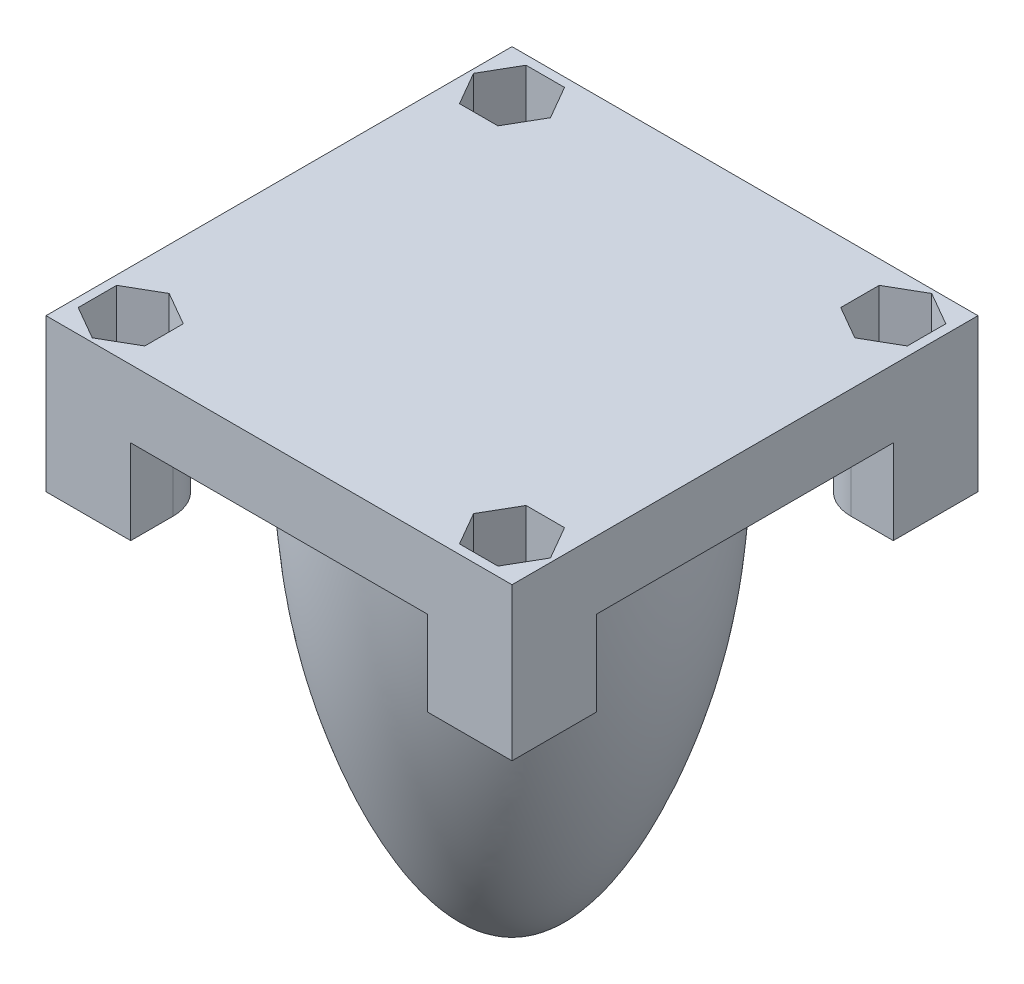
SolidWorks part; units mm, degrees
ref_plane "Front Plane" through (0, 0, 0) normal (0, 0, 1) x (1, 0, 0)
ref_plane "Top Plane" through (0, 0, 0) normal (0, 1, 0) x (1, 0, 0)
ref_plane "Right Plane" through (0, 0, 0) normal (1, 0, 0) x (0, 0, -1)
sketch "Sketch5" plane through (0, 0, 0) normal (0, 0, 1) x (1, 0, 0)
  line L0 (0, -5) -> (0, 0) construction
  line L2 (27.5, -5) -> (-27.5, -5)
  line L3 (27.5, -5) -> (27.5, 65)
  line L4 (27.5, 65) -> (-27.5, 65)
  line L5 (-27.5, -5) -> (-27.5, 65)
  line L6 (27.5, -5) -> (-27.5, 65) construction
  line L7 (27.5, 65) -> (-27.5, -5) construction
  dimension "D1" = 55
  dimension "D2" = 70
  dimension "D3" = 5
extrude "Boss-Extrude8" add sketch "Sketch5" along normal mid plane 55
sketch "Sketch1" plane through (0, 0, 0) normal (1, 0, 0) x (0, 0, -1)
  line L0 (2.2, 0) -> (4.9945, 0) construction
  line L1 (23, 55) -> (20, 55) construction
  line L2 (0, -7) -> (0, 3)
  line L3 (0, 0) -> (0, 78.0585) construction
  line L4 (23.4, 55) -> (23, 55) construction
  line L5 (0, 3) -> (-8.2525, 3) construction
  line L6 (25.4, 57) -> (304.8069, 57)
  line L7 (304.8069, 57) -> (304.8069, -311.2674)
  line L8 (304.8069, -311.2674) -> (0, -311.2674)
  line L9 (0, -311.2674) -> (0, -7)
  line L10 (2.2, 0) -> (2.2, -7) construction
  line L14 (20, 55) -> (20, 57)
  line L17 (22, 59) -> (23.4, 59)
  line L19 (2.2, -7) -> (0, -7) construction
  arc A0 (20, 57) -> (22, 59) centre (22, 57) cw
  arc A1 (25.4, 57) -> (23.4, 55) centre (23.4, 57) cw construction
  arc A2 (25.4, 57) -> (23.4, 59) centre (23.4, 57) ccw
  spline S0 degree 2 poles (23, 55) (21.456, 13.7963) (4.9945, 0) knots 0 0 0 1 1 1 construction
  spline S1 degree 3 poles (20, 55) (20, 43.9577) (18.5158, 25.9427) (6.738, 3) (0, 3) knots 0 0 0 0 0.518417 1 1 1 1
  dimension "D4" = 2.2
  dimension "D5" = 7
  dimension "D1" = 2
  dimension "D3" = 7
  dimension "D6" = 66
  dimension "D8" = 0.4
  dimension "D2" = 22
  dimension "D9" = 3
  dimension "D10" = 3
revolve "Cut-Revolve1" cut sketch "Sketch1" angle 360 about L3
sketch "Sketch6" plane through (0, 57, 0) normal (0, -1, 0) x (1, 0, 0)
  line L1 (-27.5, 27.5) -> (-17.5, 27.5)
  line L2 (-27.5, 27.5) -> (-27.5, 17.5)
  line L3 (-27.5, 17.5) -> (-17.5, 17.5)
  line L4 (-17.5, 27.5) -> (-17.5, 17.5)
  dimension "D1" = 10
  dimension "D2" = 10
extrude "Boss-Extrude9" add sketch "Sketch6" along normal blind 10
sketch "Sketch7" plane through (0, 47, 0) normal (0, -1, 0) x (1, 0, 0)
  line L0 (-22.5, 27.5) -> (-22.5, 22.5) construction
  line L2 (-17.5, 27.5) -> (-27.5, 27.5) construction
  line L4 (-22.5, 22.5) -> (-27.5, 22.5) construction
  line L5 (-27.5, 27.5) -> (-27.5, 17.5) construction
  circle A0 centre (-22.5, 22.5) radius 1.75
  dimension "D1" = 3.5
extrude "Cut-Extrude2" cut sketch "Sketch7" against normal through all
sketch "Sketch8" plane through (0, 65, 0) normal (0, 1, 0) x (1, 0, 0)
  line L0 (-22.5, -22.5) -> (-22.5, -27.038) construction
  line L1 (-22.5, -17.962) -> (-26.43, -20.231)
  line L2 (-26.43, -20.231) -> (-26.43, -24.769)
  line L3 (-26.43, -24.769) -> (-22.5, -27.038)
  line L4 (-22.5, -27.038) -> (-18.57, -24.769)
  line L5 (-18.57, -24.769) -> (-18.57, -20.231)
  line L6 (-18.57, -20.231) -> (-22.5, -17.962)
  circle A0 centre (-22.5, -22.5) radius 3.93 construction
  dimension "D1" = 7.86
extrude "Cut-Extrude3" cut sketch "Sketch8" against normal blind 7
ref_axis "Axis1" through (0, 78.6, 0) along (0, -1, 0)
pattern_circular "CirPattern1" count 4 over 360 about axis through (0, 78.6, 0) along (0, -1, 0) of "Cut-Extrude3", "Boss-Extrude9", "Cut-Extrude2"
fillet "Fillet1" radius 5 4 edges at (-17.5, 52, 17.5) (17.5, 52, 17.5) (17.5, 52, -17.5) (-17.5, 52, -17.5)
